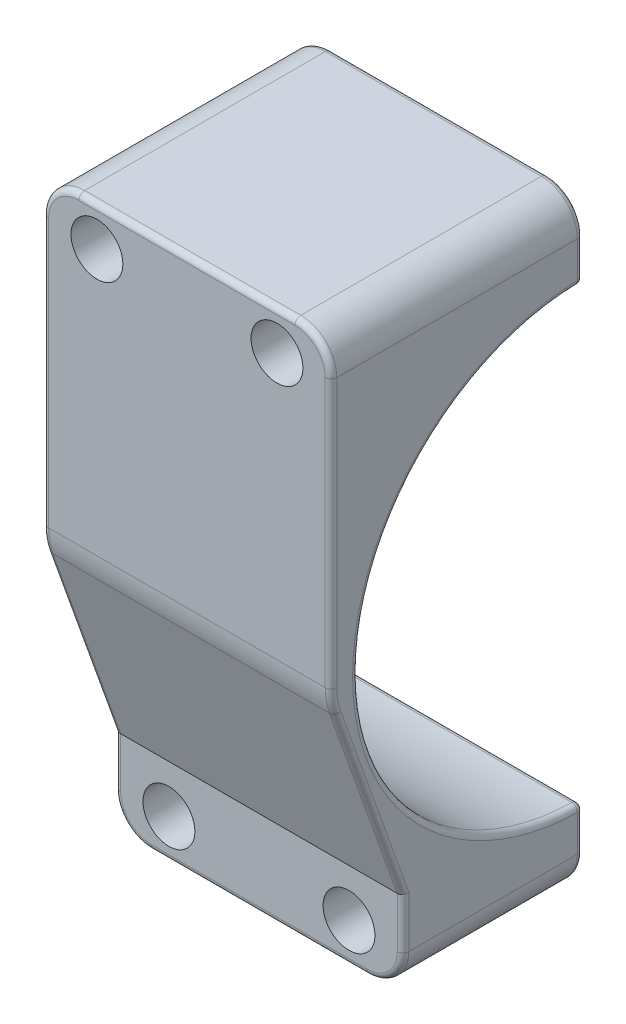
SolidWorks part; units mm, degrees
ref_plane "Front Plane" through (0, 0, 0) normal (0, 0, 1) x (1, 0, 0)
ref_plane "Top Plane" through (0, 0, 0) normal (0, 1, 0) x (1, 0, 0)
ref_plane "Right Plane" through (0, 0, 0) normal (1, 0, 0) x (0, 0, -1)
sketch "Sketch1" plane through (0, 0, 0) normal (1, 0, 0) x (0, 0, -1)
  line L0 (0, 0) -> (0, 53.34)
  line L1 (0, 53.34) -> (-22.225, 53.34)
  line L2 (-22.225, 53.34) -> (-22.225, 46.482)
  line L3 (0, 0) -> (-22.225, 0)
  line L4 (-22.225, 0) -> (-22.225, 6.858)
  arc A0 (-22.225, 6.858) -> (-22.225, 46.482) centre (-22.225, 26.67) ccw
  point P17 (0, 26.67)
  dimension "D1" = 39.624
  dimension "D2" = 22.225
  dimension "D3" = 53.34
extrude "Boss-Extrude1" add sketch "Sketch1" along normal blind 25.4
sketch "Sketch5" plane through (0, 0, 22.225) normal (0, 0, 1) x (1, 0, 0)
  line L0 (12.7, 53.34) -> (12.7, 0) construction
  line L1 (25.4, 53.34) -> (0, 53.34) construction
  line L2 (25.4, 0) -> (0, 0) construction
  line L3 (0, 49.911) -> (25.4, 49.911) construction
  line L4 (0, 53.34) -> (0, 46.482) construction
  line L5 (25.4, 53.34) -> (25.4, 46.482) construction
  line L6 (0, 3.429) -> (25.4, 3.429) construction
  line L7 (0, 6.858) -> (0, 0) construction
  line L8 (25.4, 6.858) -> (25.4, 0) construction
  point P0 (4.7625, 49.911)
  point P1 (20.6375, 49.911)
  point P2 (20.6375, 3.429)
  point P3 (4.7625, 3.429)
  dimension "D1" = 15.875
hole_wizard "#8 (0.18) Diameter Hole1" positions "Sketch5" profile "Sketch7" hole size "#8" standard "ANSI Inch" end condition through all
sketch "Sketch7" plane through (4.7625, 49.911, 22.225) normal (1, 0, 0) x (0, -1, 0)
  line L0 (0, 0) -> (0, 22.225)
  line L1 (0, 22.225) -> (2.286, 22.225)
  line L2 (2.286, 22.225) -> (2.286, 0)
  line L5 (2.286, 0) -> (0, 0)
  line L11 (0, -6.35) -> (0, 107.95) construction
  dimension "Thru Hole Dia." = 4.572
  dimension "Thru Hole Depth" = 22.225
mirror "Mirror1" about plane through (25.4, 53.34, 22.225) normal (0, 0, -1) of "#8 (0.18) Diameter Hole1", "Boss-Extrude1"
sketch "Sketch8" plane through (0, 0, 0) normal (-1, 0, 0) x (0, 0, 1)
  line L0 (44.45, 0) -> (0, 0) construction
  line L1 (0, 53.34) -> (22.225, 53.34)
  line L2 (0, 53.34) -> (0, 0)
  line L3 (0, 0) -> (22.225, 0)
  line L4 (22.225, 53.34) -> (22.225, 0)
  point P7 (22.225, 0)
extrude "Cut-Extrude1" cut sketch "Sketch8" against normal through all
sketch "Sketch2" [suppressed] plane through (0, 0, 22.225) normal (0, 0, 1) x (1, 0, 0)
  line L0 (25.4, 53.34) -> (0, 53.34) construction
  line L1 (12.7, 53.34) -> (12.7, 0) construction
  line L2 (25.4, 0) -> (0, 0) construction
  point P0 (12.7, 44.45)
  dimension "D1" = 8.89
hole_wizard "CBORE for #8 Binding Head Machine Screw1" [suppressed] positions "Sketch2" profile "Sketch4" counterbore size "#8" standard "ANSI Inch"
sketch "Sketch4" plane through (12.7, 44.45, 22.225) normal (1, 0, 0) x (0, -1, 0)
  line L0 (0, 0) -> (0, 22.225)
  line L1 (0, 22.225) -> (2.2479, 22.225)
  line L3 (2.2479, 22.225) -> (2.2479, 15.875)
  line L4 (2.2479, 15.875) -> (4.7625, 15.875)
  line L5 (4.7625, 15.875) -> (4.7625, 0)
  line L7 (4.7625, 0) -> (0, 0)
  line L11 (0, -6.35) -> (0, 107.95) construction
  dimension "Thru Hole Dia." = 4.4958
  dimension "Thru Hole Depth" = 22.225
  dimension "C'Bore Dia." = 9.525
  dimension "C'Bore Depth" = 15.875
sketch "Sketch9" plane through (25.4, 0, 0) normal (1, 0, 0) x (0, 0, -1)
  line L0 (-44.45, 0) -> (-38.1, 0)
  line L1 (-44.45, 0) -> (-22.225, 0) construction
  line L3 (-44.45, 0) -> (-44.45, 53.34) construction
  line L4 (-44.45, 25.4) -> (-44.45, 0)
  line L5 (-38.1, 0) -> (-38.1, 7.62)
  line L6 (-38.1, 7.62) -> (-44.45, 25.4)
  dimension "D1" = 6.35
  dimension "D2" = 25.4
  dimension "D3" = 7.62
extrude "Cut-Extrude2" cut sketch "Sketch9" against normal through all
fillet "Fillet1" radius 3.175 4 edges at (0, 0, 30.1625) (25.4, 0, 30.1625) (25.4, 53.34, 33.3375) (0, 53.34, 33.3375)
fillet "Fillet2" [suppressed] radius 0.508
fillet "Fillet3" radius 0.508 26 edges at (0, 37.7825, 44.45) (25.4, 37.7825, 44.45) (0, 16.51, 41.275) (25.4, 16.51, 41.275) (12.7, 0, 38.1) (12.7, 0, 22.225) (25.4, 5.0165, 22.225) (0, 5.0165, 22.225) (24.4701, 0.9299, 22.225) (0.9299, 0.9299, 22.225) (0, 5.3975, 38.1) (25.4, 5.3975, 38.1) (24.4701, 0.9299, 38.1) (0.9299, 0.9299, 38.1) (12.7, 53.34, 44.45) (0.9299, 52.4101, 44.45) (24.4701, 52.4101, 44.45) (12.7, 53.34, 22.225) (0.9299, 52.4101, 22.225) (24.4701, 52.4101, 22.225) (25.4, 26.67, 42.037) (0, 26.67, 42.037) (0, 48.3235, 22.225) (12.7, 46.482, 22.225) (25.4, 48.3235, 22.225) (12.7, 6.858, 22.225)
fillet "Fillet4" radius 6.35 3 edges at (25.2512, 25.4258, 44.3012) (0.1488, 25.4258, 44.3012) (12.7, 25.4, 44.45)
